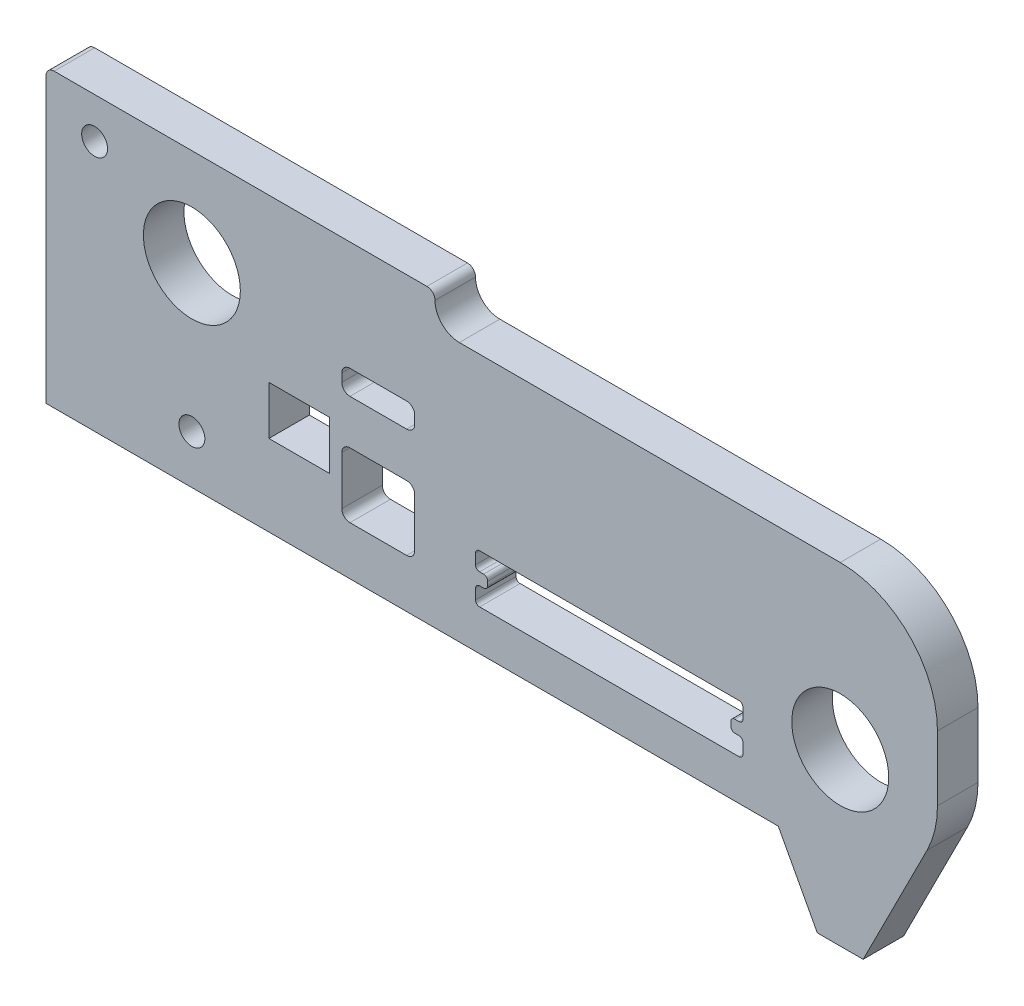
SolidWorks part; units mm, degrees
material "6061-T6 Black anodised"
ref_plane "Front Plane" through (0, 0, 0) normal (0, 0, 1) x (1, 0, 0)
ref_plane "Top Plane" through (0, 0, 0) normal (0, 1, 0) x (1, 0, 0)
ref_plane "Right Plane" through (0, 0, 0) normal (1, 0, 0) x (0, 0, -1)
sketch "Sketch1" plane through (0, 0, 0) normal (0, 0, 1) x (1, 0, 0)
  line L0 (72.3566, -24) -> (77.1721, -33)
  line L1 (-18, 12) -> (30, 12)
  line L2 (-18, 12) -> (-18, -24)
  line L3 (-18, -24) -> (72.3566, -24)
  line L4 (92, -4) -> (92, -12)
  line L5 (77.1721, -33) -> (82.8279, -33)
  line L6 (90.7087, -17.4151) -> (82.8279, -33)
  line L7 (27.5, -4.5) -> (27.5, -10) construction
  line L8 (18.5, -10) -> (27.5, -10)
  line L9 (18.5, -10) -> (18.5, -18)
  line L10 (18.5, -18) -> (27.5, -18)
  line L11 (27.5, -10) -> (27.5, -18)
  line L12 (18.5, -1.5) -> (27.5, -1.5)
  line L13 (18.5, -1.5) -> (18.5, -4.5)
  line L14 (18.5, -4.5) -> (27.5, -4.5)
  line L15 (27.5, -1.5) -> (27.5, -4.5)
  line L16 (30, 12) -> (30, 8)
  line L17 (9.5, -8) -> (17, -8)
  line L18 (9.5, -8) -> (9.5, -14)
  line L19 (9.5, -14) -> (17, -14)
  line L20 (17, -8) -> (17, -14)
  line L21 (30, 8) -> (80, 8)
  circle A0 centre (0, 0) radius 5.98
  circle A1 centre (80, -12) radius 5.98
  arc A3 (90.7087, -17.4151) -> (92, -12) centre (80, -12) ccw
  circle A4 centre (-12, 7) radius 1.6
  circle A5 centre (0, -18) radius 1.6
  arc A6 (92, -4) -> (80, 8) centre (80, -4) ccw
  point P4 (-18, -6)
  point P13 (80, -33)
  point P29 (27.5, -10)
  dimension "D3" = 11.96
  dimension "D4" = 80
  dimension "D8" = 3.2
  dimension "D10" = 13
  dimension "D11" = 10
  dimension "D12" = 12
  dimension "D23" = 12
  dimension "D1" = 9
  dimension "D5" = 18
  dimension "D6" = 36
  dimension "D7" = 4
  dimension "D9" = 12
  dimension "D13" = 5.5
  dimension "D14" = 8
  dimension "D15" = 3
  dimension "D16" = 9
  dimension "D17" = 18.5
  dimension "D18" = 10
  dimension "D19" = 9
  dimension "D20" = 7.5
  dimension "D21" = 8
  dimension "D22" = 6
  dimension "D24" = 48
  dimension "D25" = 12
  dimension "D26" = 24
extrude "Boss-Extrude1" add sketch "Sketch1" along normal blind 5
fillet "Fillet1" radius 1 8 edges at (18.5, -4.5, 2.5) (18.5, -1.5, 2.5) (27.5, -1.5, 2.5) (27.5, -4.5, 2.5) (27.5, -18, 2.5) (27.5, -10, 2.5) (18.5, -10, 2.5) (18.5, -18, 2.5)
fillet "Fillet2" radius 3 1 edges at (30, 8, 2.5)
fillet "Fillet3" radius 1 2 edges at (30, 12, 2.5) (-18, 12, 2.5)
sketch "Sketch2" plane through (0, 0, 5) normal (0, 0, 1) x (1, 0, 0)
  line L0 (35, -13) -> (68, -19) construction
  line L1 (35, -13) -> (68, -13)
  line L2 (35, -13) -> (35, -15.25)
  line L3 (35, -19) -> (68, -19)
  line L4 (68, -13) -> (68, -15.25)
  line L5 (36.5, -15.25) -> (35, -15.25)
  line L6 (36.5, -15.25) -> (36.5, -16.75)
  line L7 (36.5, -16.75) -> (35, -16.75)
  line L8 (68, -16.75) -> (68, -19)
  line L9 (36.5, -15.25) -> (35, -16.75) construction
  line L10 (36.5, -16.75) -> (35, -15.25) construction
  line L11 (66.5, -15.25) -> (68, -15.25)
  line L12 (66.5, -15.25) -> (66.5, -16.75)
  line L13 (66.5, -16.75) -> (68, -16.75)
  line L14 (-18, -24) -> (72.3566, -24) construction
  line L15 (66.5, -15.25) -> (68, -16.75) construction
  line L16 (66.5, -16.75) -> (68, -15.25) construction
  line L17 (68, -13) -> (35, -19) construction
  line L18 (35, -16.75) -> (35, -19)
  point P4 (35.75, -16)
  point P9 (67.25, -16)
  point P14 (51.5, -16)
  dimension "D1" = 1.5
  dimension "D2" = 33
  dimension "D3" = 6
  dimension "D4" = 1.5
  dimension "D5" = 68
  dimension "D6" = 5
extrude "Cut-Extrude1" cut sketch "Sketch2" against normal through all
fillet "Fillet4" radius 0.5 12 edges at (68, -13, 2.5) (68, -15.25, 2.5) (66.5, -15.25, 2.5) (66.5, -16.75, 2.5) (68, -16.75, 2.5) (68, -19, 2.5) (35, -19, 2.5) (35, -16.75, 2.5) (35, -13, 2.5) (35, -15.25, 2.5) (36.5, -16.75, 2.5) (36.5, -15.25, 2.5)
equation "\"y-cross-rib-thickness\"=4"
equation "\"y-rib-thickness\"=6"
equation "\"bed-plate-thickness\"=3"
equation "\"x-plate-thickness\"=5"
equation "\"rod-diameter\"=12"
equation "\"t-nut-hole-diameter\"=3"
equation "\"y-plate-thickness\"=5"
equation "\"D1@Boss-Extrude1\"=\"y-plate-thickness\""
